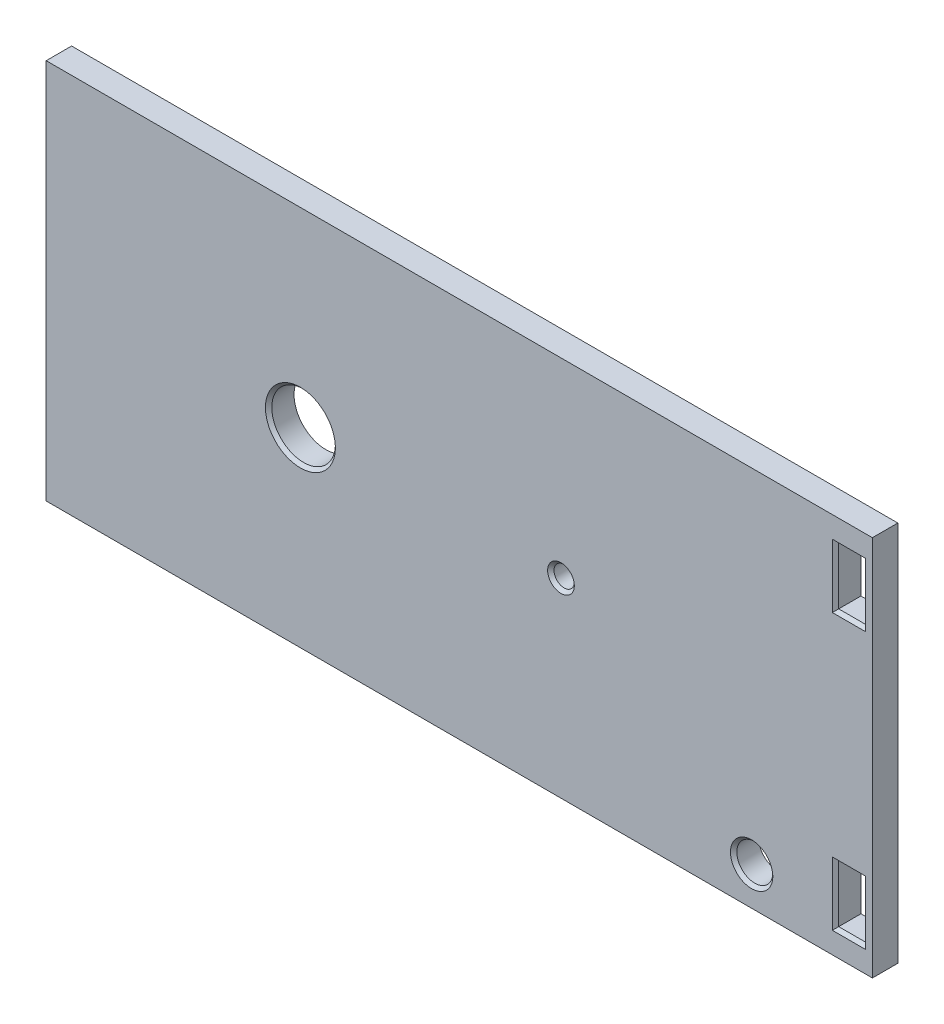
SolidWorks part; units mm, degrees
ref_plane "Front Plane" through (0, 0, 0) normal (0, 0, 1) x (1, 0, 0)
ref_plane "Top Plane" through (0, 0, 0) normal (0, 1, 0) x (1, 0, 0)
ref_plane "Right Plane" through (0, 0, 0) normal (1, 0, 0) x (0, 0, -1)
sketch "Sketch1" plane through (0, 0, 0) normal (0, 0, 1) x (1, 0, 0)
  line L2 (-65, -30) -> (-65, 30)
  line L12 (61.3, 26.15) -> (61.3, 17.15) construction
  line L13 (-65, 30) -> (65, 30)
  line L15 (-65, -30) -> (65, -30)
  line L16 (65, 30) -> (65, -30)
  line L17 (59.2, 26.15) -> (63.4, 26.15)
  line L18 (59.2, 26.15) -> (59.2, 17.15)
  line L19 (59.2, 17.15) -> (63.4, 17.15)
  line L20 (63.4, 26.15) -> (63.4, 17.15)
  line L21 (59.2, -17.15) -> (63.4, -17.15)
  line L22 (59.2, -17.15) -> (59.2, -26.15)
  line L23 (59.2, -26.15) -> (63.4, -26.15)
  line L24 (63.4, -17.15) -> (63.4, -26.15)
  line L25 (61.3, -17.15) -> (61.3, -26.15) construction
  line L26 (63.4, 21.65) -> (59.2, 21.65) construction
  line L27 (63.4, -21.65) -> (59.2, -21.65) construction
  circle A3 centre (-25, 0) radius 5
  circle A4 centre (46, -24) radius 2.83
  circle A6 centre (16, 0) radius 1.6
  point P2 (0, 30)
  point P9 (65, 0)
  dimension "D6" = 10
  dimension "D4" = 5.66
  dimension "D2" = 60
  dimension "D3" = 130
  dimension "D8" = 24
  dimension "D1" = 9
  dimension "D9" = 4.2
  dimension "D10" = 21.65
  dimension "D11" = 21.65
  dimension "D5" = 40
  dimension "D7" = 86.3
  dimension "D12" = 71
  dimension "D13" = 41
extrude "Boss-Extrude1" add sketch "Sketch1" along normal mid plane 4
chamfer "Chamfer1" distance 0.5 angle 45 11 edges at (61.3, 17.15, 2) (59.2, 21.65, 2) (61.3, 26.15, 2) (63.4, 21.65, 2) (-20, 0, 2) (48.83, -24, 2) (61.3, -26.15, 2) (59.2, -21.65, 2) (61.3, -17.15, 2) (63.4, -21.65, 2) (17.6, 0, 2)
sketch "Sketch3" plane through (0, 0, -2) normal (0, 0, -1) x (-1, 0, 0)
  line L0 (-61.3, 26.15) -> (-61.3, 17.15) construction
  line L1 (-63.4, 21.65) -> (-59.2, 21.65) construction
  line L2 (-61.3, -17.15) -> (-61.3, -26.15) construction
  line L3 (-59.2, -17.15) -> (-63.4, -17.15) construction
  line L4 (-63.4, -21.65) -> (-59.2, -21.65) construction
equation "\"hole_width\"=3.4"
equation "\"hole_length\"=8.7"
equation "\"pin_hole_height\"=9"
equation "\"D1@Sketch1\"=\"pin_hole_height\""
equation "\"pin_hole_width\"=4.2"
equation "\"D9@Sketch1\"=\"pin_hole_width\""
equation "\"wall_thick_ness\"=4"
equation "\"D1@Boss-Extrude1\"=\"wall_thick_ness\""
equation "\"back_boost\"= 7"
equation "\"D5@Sketch1\"=\"back_boost\"+33.00mm"
equation "\"D3@Sketch1\"=123.00mm+\"back_boost\""
